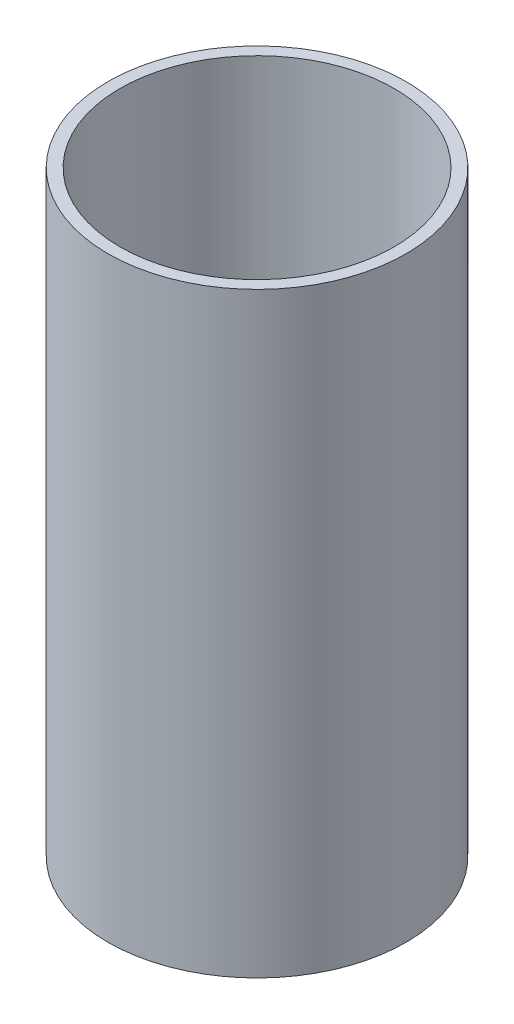
SolidWorks part; units mm, degrees
material "AISI 304"
ref_plane "Спереди" through (0, 0, 0) normal (0, 0, 1) x (1, 0, 0)
ref_plane "Сверху" through (0, 0, 0) normal (0, 1, 0) x (1, 0, 0)
ref_plane "Справа" through (0, 0, 0) normal (1, 0, 0) x (0, 0, -1)
ref_axis "ОсьX" through (-88.99, 0, 0) along (1, 0, 0)
ref_axis "ОсьZ" through (0, 55, 0) along (0, -1, 0)
ref_axis "ОсьY" through (0, 0, -88.99) along (0, 0, 1)
sketch "Эскиз1" plane through (0, 0, 0) normal (0, 0, 1) x (1, 0, 0)
  line L0 (-50, 200) -> (-50, 0)
  line L1 (0, 26.169) -> (0, -22.1581) construction
  dimension "D1" = 100
  dimension "D2" = 200
revolve "Повернуть-Тонкостенный1" add sketch "Эскиз1" angle 360 about L1 wall 4
